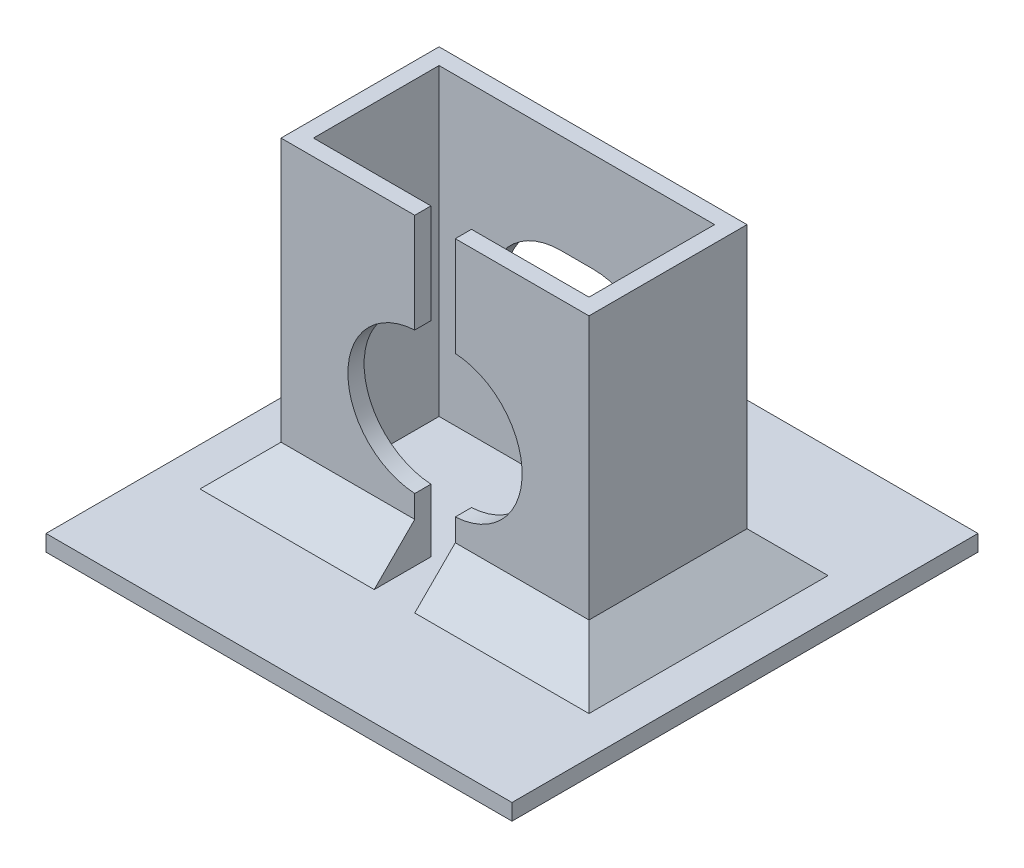
SolidWorks part; units mm, degrees
ref_plane "Front Plane" through (0, 0, 0) normal (0, 0, 1) x (1, 0, 0)
ref_plane "Top Plane" through (0, 0, 0) normal (0, 1, 0) x (1, 0, 0)
ref_plane "Right Plane" through (0, 0, 0) normal (1, 0, 0) x (0, 0, -1)
sketch "Sketch1" plane through (0, 0, 0) normal (0, 1, 0) x (1, 0, 0)
  line L1 (0, 0) -> (68, 0)
  line L2 (0, 0) -> (0, 31)
  line L3 (0, 31) -> (68, 31)
  line L4 (68, 0) -> (68, 31)
  line L5 (-23.5, 72.5) -> (91.5, 72.5)
  line L6 (-23.5, 72.5) -> (-23.5, -42.5)
  line L7 (-23.5, -42.5) -> (91.5, -42.5)
  line L8 (91.5, 72.5) -> (91.5, -42.5)
  line L12 (-4, -4) -> (72, -4)
  line L13 (-4, -4) -> (-4, 35)
  line L14 (-4, 35) -> (72, 35)
  line L15 (72, -4) -> (72, 35)
  point P13 (0, 0)
  dimension "D1" = 68
  dimension "D2" = 31
  dimension "D3" = 115
  dimension "D4" = 23.5
  dimension "D5" = 42.5
  dimension "D6" = 76
  dimension "D7" = 39
  dimension "D8" = 4
  dimension "D9" = 4
extrude "Boss-Extrude2" add sketch "Sketch1" along normal blind 75 contours L2 L3 L4 L1 | L14 L15 L12 L13
extrude "Boss-Extrude6" add sketch "Sketch1<9>" against normal blind 4 contours L8 L5 L6 L7 L15 L12 L13 L14 | L12 L15 L14 L13 L4 L1 L2 L3 | L1 L4 L3 L2 region at (34, 0, -15.5) region at (34, 0, -70.8737) region at (-3.1458, 0, -15.5)
sketch "Sketch1<9>" plane through (0, 0, 0) normal (0, 1, 0) x (1, 0, 0) same geometry as "Sketch1"
sketch "Sketch7" plane through (0, 0, 4) normal (0, 0, 1) x (1, 0, 0)
  line L0 (-4, 0) -> (72, 0) construction
  line L3 (30, 33) -> (38, 33) construction
  line L4 (30, 50.5) -> (38, 50.5)
  line L5 (30, 15.5) -> (38, 15.5)
  line L6 (-4, 75) -> (-4, 0) construction
  arc A2 (30, 50.5) -> (30, 15.5) centre (30, 33) ccw
  arc A3 (38, 15.5) -> (38, 50.5) centre (38, 33) ccw
  point P0 (0, 0)
  point P7 (0, 0)
  point P15 (34, 33)
  dimension "D1" = 33
  dimension "D2" = 38
sketch "Sketch9" plane through (0, 0, 4) normal (0, 0, 1) x (1, 0, 0)
  line L0 (-4, 75) -> (72, 75) construction
  line L1 (-4, 0) -> (72, 0) construction
  line L2 (29, 75) -> (39, 75)
  line L3 (29, 75) -> (29, 0)
  line L4 (29, 0) -> (39, 0)
  line L5 (39, 75) -> (39, 0)
  line L6 (-4, 75) -> (-4, 0) construction
  dimension "D1" = 10
  dimension "D2" = 33
extrude "Cut-Extrude2" cut sketch "Sketch9" against normal blind 6
extrude "Cut-Extrude3" cut sketch "Sketch7" against normal blind 52
chamfer "Chamfer1" distance 10 angle 45 5 edges at (12.5, 0, 4) (-4, 0, -15.5) (55.5, 0, 4) (72, 0, -15.5) (34, 0, -35)
